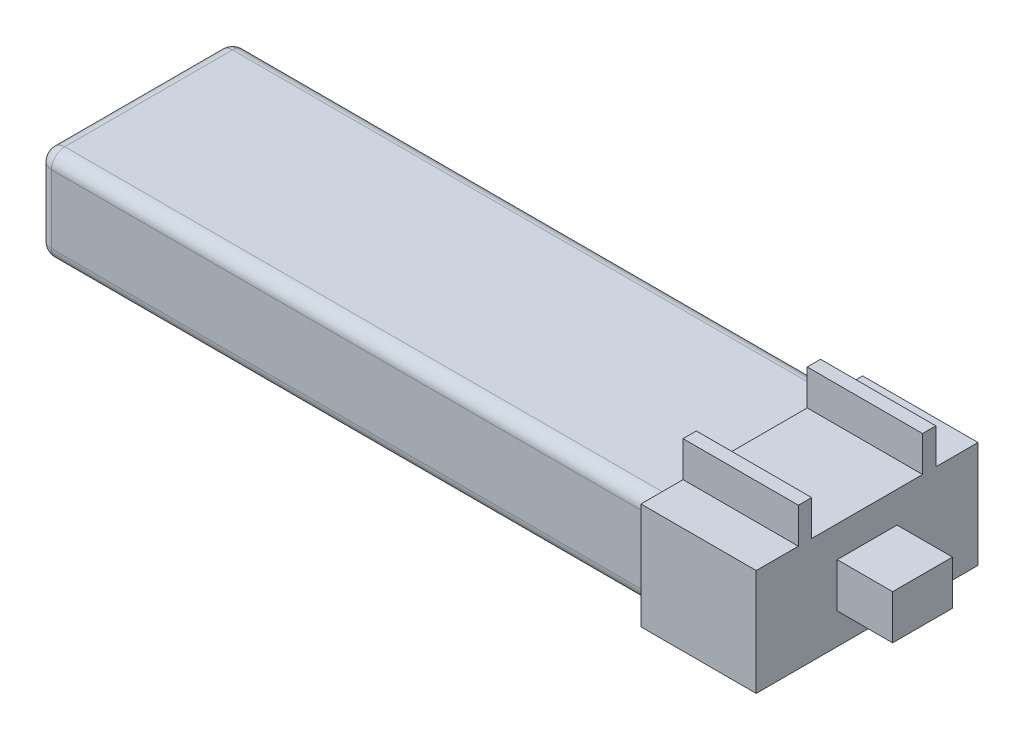
SolidWorks part; units mm, degrees
ref_plane "Front Plane" through (0, 0, 0) normal (0, 0, 1) x (1, 0, 0)
ref_plane "Top Plane" through (0, 0, 0) normal (0, 1, 0) x (1, 0, 0)
ref_plane "Right Plane" through (0, 0, 0) normal (1, 0, 0) x (0, 0, -1)
sketch "Sketch1" plane through (0, 0, 0) normal (0, 1, 0) x (1, 0, 0)
  line L1 (-20.955, -6.35) -> (20.955, -6.35)
  line L2 (-20.955, -6.35) -> (-20.955, 6.35)
  line L3 (-20.955, 6.35) -> (20.955, 6.35)
  line L4 (20.955, -6.35) -> (20.955, 6.35)
  line L5 (-20.955, -6.35) -> (20.955, 6.35) construction
  line L6 (-20.955, 6.35) -> (20.955, -6.35) construction
  point P0 (0, 0)
  dimension "D1" = 41.91
  dimension "D2" = 12.7
extrude "Boss-Extrude1" add sketch "Sketch1" along normal mid plane 6.096
sketch "Sketch2" plane through (20.955, 0, 0) normal (1, 0, 0) x (0, 0, -1)
  line L0 (-3.937, 0) -> (3.937, 0)
  line L1 (-3.937, 0) -> (-3.937, 5.08)
  line L2 (-3.937, 5.08) -> (-3.175, 5.08)
  line L3 (-3.175, 5.08) -> (-3.175, 0)
  line L4 (-6.35, 3.048) -> (6.35, 3.048) construction
  line L5 (0, 0) -> (0, 6.5508) construction
  line L6 (3.937, 0) -> (3.937, 5.08)
  line L7 (3.175, 5.08) -> (3.175, 0)
  line L8 (3.937, 5.08) -> (3.175, 5.08)
  line L10 (-1.7145, -1.27) -> (1.7145, -1.27)
  line L11 (-1.7145, -1.27) -> (-1.7145, 1.27)
  line L12 (-1.7145, 1.27) -> (1.7145, 1.27)
  line L13 (1.7145, -1.27) -> (1.7145, 1.27)
  line L14 (-1.7145, -1.27) -> (1.7145, 1.27) construction
  line L15 (-1.7145, 1.27) -> (1.7145, -1.27) construction
  point P4 (0, 0)
  line M8 (6.35, 3.048) -> (-6.35, 3.048)
  dimension "D1" = 3.175
  dimension "D2" = 0.762
  dimension "D3" = 2.032
  dimension "D4" = 2.54
  dimension "D5" = 3.429
extrude "Boss-Extrude2" add sketch "Sketch2" against normal blind 6.604 contours L3 L2 L1 M8 | L6 L8 L7 M8 region at (20.955, 4.064, 3.556) region at (20.955, 4.064, -3.556)
extrude "Boss-Extrude3" add sketch "Sketch2<3>" along normal blind 3.175 contours L0 L13 L12 L11 | L10 L13 L0 L11 region at (20.955, 0.635, 0) region at (20.955, -0.635, 0)
sketch "Sketch2<3>" plane through (20.955, 0, 0) normal (1, 0, 0) x (0, 0, -1) same geometry as "Sketch2"
sketch "Sketch4" plane through (20.955, 0, 0) normal (1, 0, 0) x (0, 0, -1)
  line L1 (-5.5626, -2.7178) -> (5.5626, -2.7178)
  line L2 (-5.5626, -2.7178) -> (-5.5626, 2.7178)
  line L3 (-5.5626, 2.7178) -> (5.5626, 2.7178)
  line L4 (5.5626, -2.7178) -> (5.5626, 2.7178)
  line L5 (-5.5626, -2.7178) -> (5.5626, 2.7178) construction
  line L6 (-5.5626, 2.7178) -> (5.5626, -2.7178) construction
  line L7 (-7.12, -3.9586) -> (7.12, -3.9586)
  line L8 (-7.12, -3.9586) -> (-7.12, 3.9586)
  line L9 (-7.12, 3.9586) -> (7.12, 3.9586)
  line L10 (7.12, -3.9586) -> (7.12, 3.9586)
  line L11 (-7.12, -3.9586) -> (7.12, 3.9586) construction
  line L12 (-7.12, 3.9586) -> (7.12, -3.9586) construction
  point P0 (0, 0)
  point P5 (0, 0)
  dimension "D1" = 5.4356
  dimension "D2" = 11.1252
extrude "Cut-Extrude1" cut sketch "Sketch4" against normal through all from surface starting at face at (14.351, 4.064, -3.556)
fillet "Fillet1" radius 0.762 8 edges at (-20.955, 0, 5.5626) (-20.955, 0, -5.5626) (-3.302, -2.7178, -5.5626) (-3.302, -2.7178, 5.5626) (-20.955, -2.7178, 0) (-20.955, 2.7178, 0) (-3.302, 2.7178, -5.5626) (-3.302, 2.7178, 5.5626)
